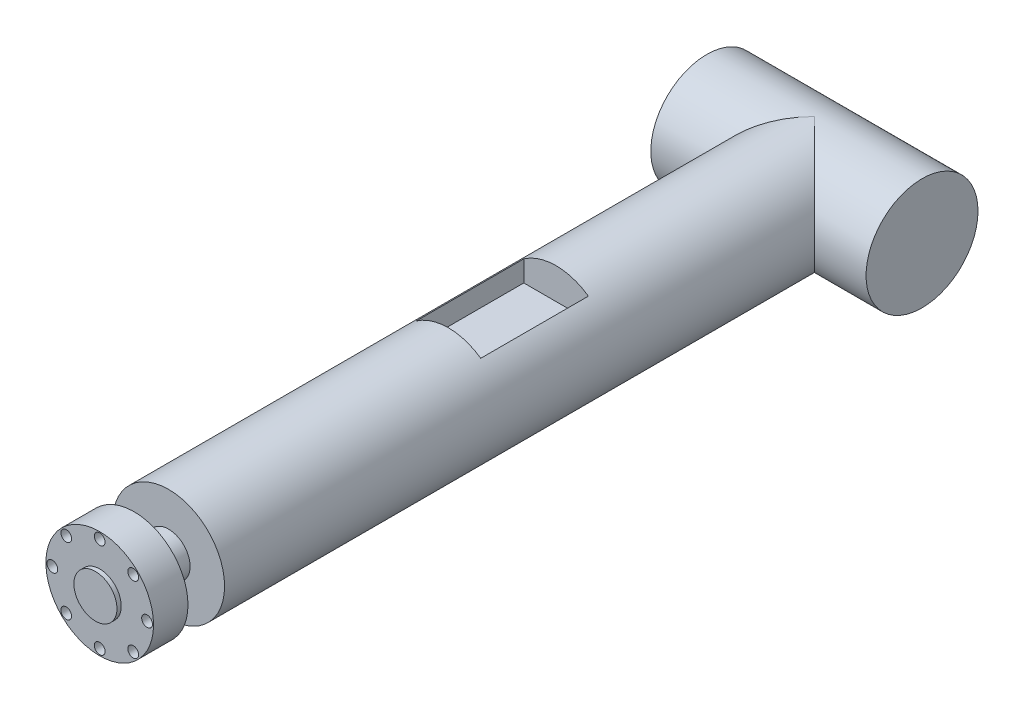
SolidWorks part; units mm, degrees
ref_plane "Ebene vorne" through (0, 0, 0) normal (0, 0, 1) x (1, 0, 0)
ref_plane "Ebene oben" through (0, 0, 0) normal (0, 1, 0) x (1, 0, 0)
ref_plane "Ebene rechts" through (0, 0, 0) normal (1, 0, 0) x (0, 0, -1)
sketch "Skizze1" plane through (0, 0, 0) normal (1, 0, 0) x (0, 0, -1)
  circle A0 centre (0, 0) radius 13
extrude "Aufsatz-Linear austragen1" add sketch "Skizze1" along normal blind 25 and the other way blind 25
sketch "Skizze2" plane through (0, 0, 0) normal (0, 0, 1) x (1, 0, 0)
  circle A0 centre (0, 0) radius 13
extrude "Aufsatz-Linear austragen2" add sketch "Skizze2" along normal blind 150
sketch "Skizze4" plane through (0, 0, 150) normal (0, 0, 1) x (1, 0, 0)
  circle A0 centre (0, 0) radius 5
extrude "Aufsatz-Linear austragen3" add sketch "Skizze4" along normal blind 16
sketch "Skizze5" plane through (0, 0, 166) normal (0, 0, 1) x (1, 0, 0)
  circle A0 centre (0, 0) radius 12.5
  dimension "D1" = 25
extrude "Aufsatz-Linear austragen4" add sketch "Skizze5" against normal blind 8
sketch "Skizze6" plane through (0, 0, 166) normal (0, 0, 1) x (1, 0, 0)
  circle A0 centre (0, 0) radius 5
extrude "Aufsatz-Linear austragen5" add sketch "Skizze6" along normal blind 1
sketch "Skizze7" plane through (0, 0, 166) normal (0, 0, 1) x (1, 0, 0)
  circle A0 centre (0, 11) radius 1.25
  circle A2 centre (7.7782, 7.7782) radius 1.25
  circle A3 centre (11, 0) radius 1.25
  circle A4 centre (7.7782, -7.7782) radius 1.25
  circle A5 centre (0, -11) radius 1.25
  circle A6 centre (-7.7782, -7.7782) radius 1.25
  circle A7 centre (-11, 0) radius 1.25
  circle A8 centre (-7.7782, 7.7782) radius 1.25
  point P2 (0, 0)
  point P21 (0, 0)
  dimension "D1" = 11
  dimension "D2" = 2.5
  dimension "D3" = 8
extrude "Schnitt-Linear austragen2" cut sketch "Skizze7" against normal up to next contours A7 | A8 | A2 | A3 | A4 | A6 | A5 | A0 region at (7.7782, 7.7782, 166) region at (11, 0, 166) region at (7.7782, -7.7782, 166) region at (0, -11, 166) region at (-7.7782, -7.7782, 166) region at (-11, 0, 166) region at (-7.7782, 7.7782, 166)
sketch3d "3D-Skizze1"
  point P0 (5.5171, 11.7712, 64.7692)
ref_plane "Ebene1" through (0, 5.7712, 0) normal (0, 1, 0) x (1, 0, 0)
sketch "Skizze8" plane through (0, 5.7712, 0) normal (0, 1, 0) x (1, 0, 0)
  line L1 (-7.5, -60) -> (7.5, -60)
  line L2 (-7.5, -60) -> (-7.5, -85)
  line L3 (-7.5, -85) -> (7.5, -85)
  line L4 (7.5, -60) -> (7.5, -85)
  line L5 (-7.5, -60) -> (7.5, -85) construction
  line L6 (-7.5, -85) -> (7.5, -60) construction
  point P0 (0, -72.5)
  point P7 (0, -60)
  dimension "D1" = 15
  dimension "D2" = 25
  dimension "D3" = 60
extrude "Schnitt-Linear austragen3" cut sketch "Skizze8" along normal up to next
